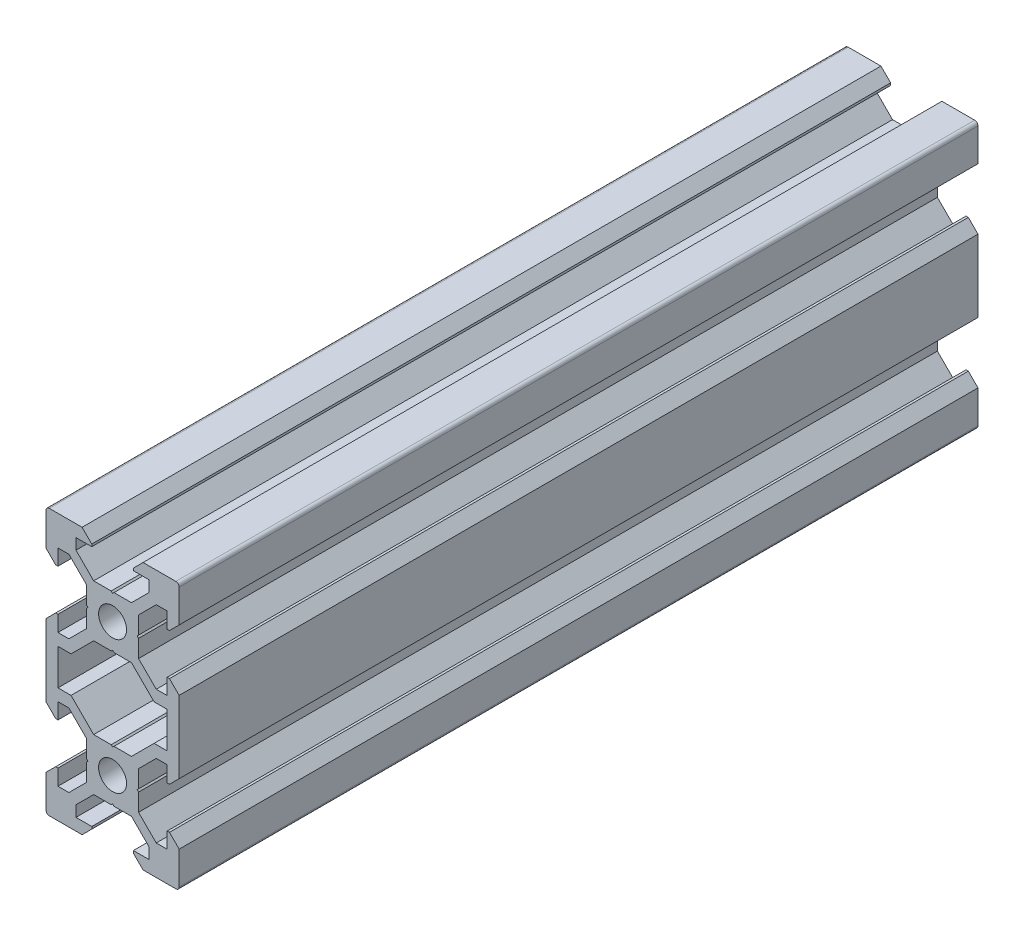
SolidWorks part; units mm, degrees
ref_plane "Plan de face" through (0, 0, 0) normal (0, 0, 1) x (1, 0, 0)
ref_plane "Plan de dessus" through (0, 0, 0) normal (0, 1, 0) x (1, 0, 0)
ref_plane "Plan de droite" through (0, 0, 0) normal (1, 0, 0) x (0, 0, -1)
ref_axis "Axe" through (0, 0, -13.782) along (0, 0, 1)
sketch "Esquisse1" plane through (0, 0, 0) normal (0, 0, 1) x (1, 0, 0)
  line L0 (0, 22.8977) -> (0, -22.8977) construction
  line L1 (-33.6074, 0) -> (33.6074, 0) construction
  line L2 (0, 0) -> (-22.2114, 22.2114) construction
  line L3 (-9.5, 10) -> (-4.58, 10)
  line L4 (-4.58, 10) -> (-3.125, 8.545)
  line L5 (-3.125, 8.545) -> (-3.125, 8.2)
  line L6 (-3.125, 8.2) -> (-5.5, 8.2)
  line L7 (-2.8393, 3.9) -> (-5.5, 6.5607)
  line L8 (-2.8393, 3.9) -> (-0.21, 3.9)
  line L9 (-5.5, 6.5607) -> (-5.5, 8.2)
  line L10 (0, 3.69) -> (0, 2.1)
  line L11 (-3.9, 2.8393) -> (-6.5607, 5.5)
  line L12 (-8.545, 3.125) -> (-8.2, 3.125)
  line L13 (-8.2, 3.125) -> (-8.2, 5.5)
  line L14 (-6.5607, 5.5) -> (-8.2, 5.5)
  line L15 (-10, 4.58) -> (-8.545, 3.125)
  line L16 (-10, 9.5) -> (-10, 4.58)
  line L17 (-0.21, 3.9) -> (0, 3.69)
  line L18 (-3.9, 2.8393) -> (-3.9, 0.21)
  line L20 (-3.9, 0.21) -> (-3.69, 0)
  line L21 (-0.21, -3.9) -> (0, -3.69)
  line L22 (0, -3.69) -> (0, -2.1)
  line L23 (-6.5607, -5.5) -> (-8.2, -5.5)
  line L24 (-2.8393, -3.9) -> (-0.21, -3.9)
  line L25 (-8.545, -3.125) -> (-8.2, -3.125)
  line L26 (-10, -4.58) -> (-8.545, -3.125)
  line L27 (-8.2, -3.125) -> (-8.2, -5.5)
  line L28 (-2.8393, -3.9) -> (-6.2393, -7.3)
  line L29 (-3.9, -2.8393) -> (-6.5607, -5.5)
  line L30 (-3.9, -2.8393) -> (-3.9, -0.21)
  line L31 (-3.9, -0.21) -> (-3.69, 0)
  line L32 (-6.2393, -7.3) -> (-8.2, -7.3)
  line L33 (-8.2, -7.3) -> (-8.2, -10)
  line L34 (-8.2, -10) -> (-10, -10)
  line L35 (-10, -10) -> (-10, -4.58)
  arc A0 (0, -2.1) -> (0, 2.1) centre (0, 0) cw
  arc A1 (-9.5, 10) -> (-10, 9.5) centre (-9.5, 9.5) ccw
  point P4 (0, 0)
  point P7 (0, 0)
  point P30 (-10, 10)
  dimension "D5" = 11
  dimension "D2" = 2.1
  dimension "D3" = 6.25
  dimension "D10" = 0.5
  dimension "D4" = 9.16
  dimension "D6" = 1.5
  dimension "D7" = 1.8
  dimension "D8" = 4.3
  dimension "D9" = 20
  dimension "D11" = 0.42
  dimension "D12" = 10
  dimension "D13" = 1.8
extrude "Boss.-Extru.1" add sketch "Esquisse1" along normal blind 120
sketch "Esquisse3" plane through (0, 0, 120) normal (0, 0, 1) x (1, 0, 0)
  line L0 (0, 0) -> (-9.8536, 9.8536) construction
  line L1 (-8.2, 8.2) -> (-8.2, 6.57)
  line L2 (-8.2, 6.57) -> (-7.54, 6.57)
  line L3 (-7.54, 6.57) -> (-6.57, 7.54)
  line L4 (-8.2, 3.125) -> (-8.2, 5.5) construction
  line L5 (-6.57, 8.2) -> (-6.57, 7.54)
  line L6 (-8.2, 8.2) -> (-6.57, 8.2)
  line L7 (-5.5, 6.5607) -> (-5.5, 8.2) construction
  arc A0 (-9.5, 10) -> (-10, 9.5) centre (-9.5, 9.5) ccw construction
  point P13 (-7.055, 7.055)
  point P14 (-6.57, 7.87)
  dimension "D1" = 1.07
extrude "Enlèv. mat.-Extru.1" [suppressed] cut sketch "Esquisse3" against normal through all
mirror "Symétrie1" about plane through (0, 3.69, 120) normal (-1, 0, 0) of "Enlèv. mat.-Extru.1", "Boss.-Extru.1"
mirror "Symétrie6" about plane through (-8.2, -10, 120) normal (0, 1, 0) of "Symétrie1", "Boss.-Extru.1"
